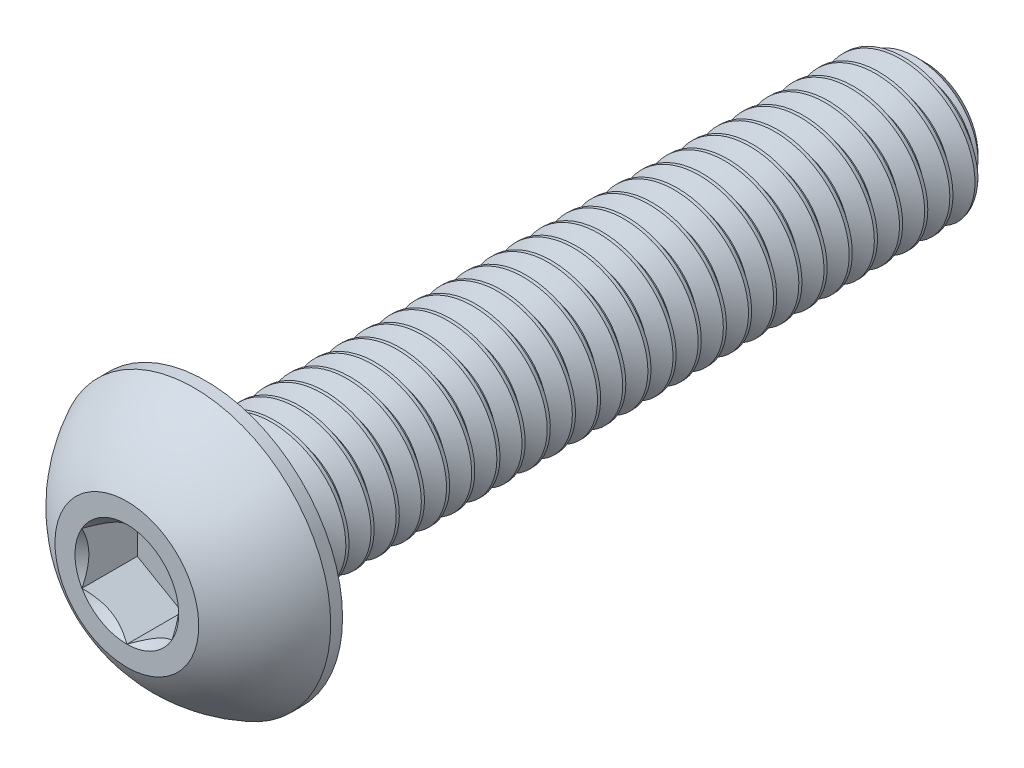
SolidWorks part; units mm, degrees
ref_plane "Front" through (0, 0, 0) normal (0, 0, 1) x (1, 0, 0)
ref_plane "Top" through (0, 0, 0) normal (0, 1, 0) x (1, 0, 0)
ref_plane "Right" through (0, 0, 0) normal (1, 0, 0) x (0, 0, -1)
sketch "Sketch1" plane through (0, 0, 0) normal (1, 0, 0) x (0, 0, -1)
  line L2 (2.2, 2) -> (22.2, 2)
  line L3 (22.2, 2) -> (22.2, 0)
  line L4 (22.2, 0) -> (2.2, 0)
  line L6 (1.87, 3.8) -> (2.2, 3.8) construction
  line L7 (22.2, 2) -> (22.2, -2) construction
  line L8 (0, 0) -> (2.2, 0) construction
  line L9 (2.2, 3.8) -> (2.2, -3.8) construction
  line L11 (2.2, 2) -> (2.2, 0)
  line L13 (0, 1.25) -> (0, -1.25) construction
  line L14 (0, 1.25) -> (0, 2) construction
  arc A3 (0, 2) -> (1.87, 3.8) centre (3.7264, 0) cw construction
  dimension "D1" = 0.33
  dimension "Head Ht" = 2.2
  dimension "Head Dia" = 7.6
  dimension "Dia" = 4
  dimension "Lg" = 20
  dimension "Hex" = 2.5
revolve "Revolve1" add sketch "Sketch1" angle 360 mid plane about L4
sketch "Sketch3" plane through (0, 0, -22.2) normal (0, 0, -1) x (-1, 0, 0)
  circle A0 centre (0, 0) radius 2
curve "Helix/Spiral1" pitch 0.7 height 20.7 radius 2 centre (0, 0, -22.2) axis (0, 0, 1) start towards (0, 1, 0)
sketch "Sketch2" plane through (0, 0, 0) normal (1, 0, 0) x (0, 0, -1)
  line L0 (22.2, 2) -> (22.8125, 2)
  line L1 (22.8125, 2) -> (22.55, 1.5453)
  line L2 (22.55, 1.5453) -> (22.4625, 1.5453)
  line L3 (22.4625, 1.5453) -> (22.2, 2)
  line L4 (22.3313, 1.7727) -> (22.6812, 1.7727) construction
  dimension "D1" = 60
  dimension "D2" = 0.0875
  dimension "D3" = 0.35
chamfer "Chamfer1" distance 0.525 angle 45 1 edges at (0, 2, -22.2)
sweep "Cut-Sweep1" cut profiles "Sketch2" path "Helix/Spiral1"
sketch "Sketch7" plane through (0, 0, 0) normal (1, 0, 0) x (0, 0, -1)
  line L6 (1.87, 3.8) -> (2.2, 3.8) construction
  line L8 (0, 0) -> (2.2, 0) construction
  line L11 (2.2, 3.8) -> (2.2, -3.8) construction
  line L12 (1.87, 3.8) -> (2.2, 3.8)
  line L13 (0, 0) -> (2.2, 0)
  line L14 (0, 1.25) -> (0, -1.25) construction
  line L15 (2.2, 3.8) -> (2.2, 0)
  line L16 (0, 2) -> (0, 0)
  arc A2 (1.87, 3.8) -> (0, 2) centre (3.7264, 0) ccw construction
  arc A3 (1.87, 3.8) -> (0, 2) centre (3.7264, 0) ccw
revolve "Revolve2" add sketch "Sketch7" angle 360 mid plane about L13
sketch "Sketch5" plane through (0, 0, 0) normal (0, 0, 1) x (1, 0, 0)
  line L1 (1.25, -0.7217) -> (1.25, 0.7217)
  line L2 (1.25, 0.7217) -> (0, 1.4434)
  line L3 (0, 1.4434) -> (-1.25, 0.7217)
  line L4 (-1.25, 0.7217) -> (-1.25, -0.7217)
  line L5 (-1.25, -0.7217) -> (0, -1.4434)
  line L6 (0, -1.4434) -> (1.25, -0.7217)
  circle A0 centre (0, 0) radius 1.25 construction
extrude "Cut-Extrude2" cut sketch "Sketch5" against normal blind 1.54
sketch "Sketch6" plane through (0, 0, 0) normal (0, 0, 1) x (1, 0, 0)
  circle A0 centre (0, 0) radius 1.4434
extrude "Cut-Extrude3" cut sketch "Sketch6" against normal blind 1.54 draft 45
sketch "Sketch9" [suppressed] plane through (0, 0, -2.2) normal (0, 0, 1) x (1, 0, 0)
  circle A2 centre (0, 0) radius 2
extrude "Boss-Extrude2" [suppressed] add sketch "Sketch9" against normal offset from surface (5 mm away) 28.575 up to face at (0, 1.475, -22.2)
sketch "Sketch10" plane through (0, 0, 0) normal (1, 0, 0) x (0, 0, -1)
  line L0 (22.2, 2) -> (22.2, -2) construction
  point P0 (21.15, -2)
  dimension "D1" = 1.05
equation "\"D3@Helix/Spiral1\" = \"Lg@Sketch1\" + \"D4@Helix/Spiral1\""
equation "\"D2@Sketch2\" = \"D4@Helix/Spiral1\" * .125"
equation "\"D3@Sketch2\" = \"D4@Helix/Spiral1\" * .5"
equation "\"D1@Chamfer1\" = \"D4@Helix/Spiral1\" * .75"
equation "\"D1@Cut-Extrude2\" = \"Head Ht@Sketch1\" * .7"
equation "\"D1@Sketch1\" = \"Head Ht@Sketch1\" * .15"
equation "\"D1@Sketch10\" = \"D4@Helix/Spiral1\" * 1.5"
equation "\"D1@Cut-Extrude3\" = \"D1@Cut-Extrude2\""
